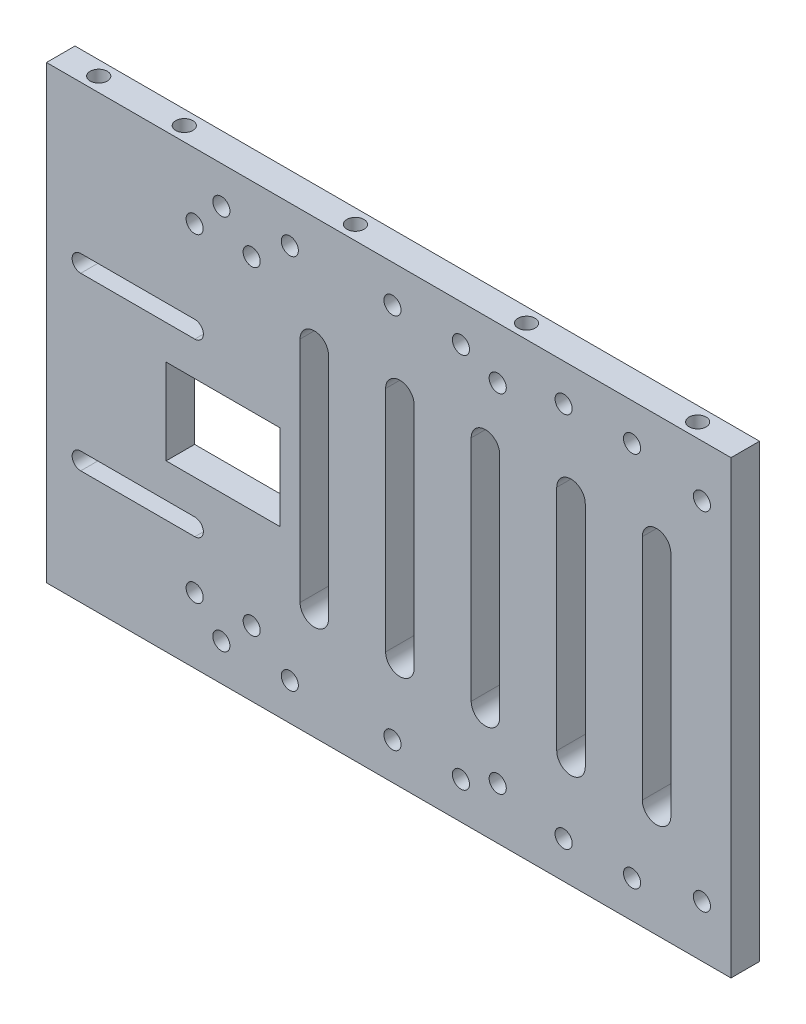
SolidWorks part; units mm, degrees
ref_plane "前视基准面" through (0, 0, 0) normal (0, 0, 1) x (1, 0, 0)
ref_plane "上视基准面" through (0, 0, 0) normal (0, 1, 0) x (1, 0, 0)
ref_plane "右视基准面" through (0, 0, 0) normal (1, 0, 0) x (0, 0, -1)
other "Configuration Table"
sketch "草图1" plane through (0, 0, 0) normal (0, 0, 1) x (1, 0, 0)
  line L1 (-60, -39.5) -> (60, -39.5)
  line L2 (-60, -39.5) -> (-60, 39.5)
  line L3 (-60, 39.5) -> (60, 39.5)
  line L4 (60, -39.5) -> (60, 39.5)
  line L5 (-60, -39.5) -> (60, 39.5) construction
  line L6 (-60, 39.5) -> (60, -39.5) construction
  point P0 (0, 0)
  dimension "D1" = 79
  dimension "D2" = 120
extrude "凸台-拉伸1" add sketch "草图1" along normal blind 5
sketch "草图2" plane through (0, 0, 0) normal (0, 0, -1) x (-1, 0, 0)
  circle A0 centre (-42.656, -33) radius 3.1
  circle A1 centre (-30.656, -33) radius 3.1
extrude "切除-拉伸1" cut sketch "草图2" against normal blind 2
sketch "草图3" plane through (0, 0, 2) normal (0, 0, -1) x (-1, 0, 0)
  circle A0 centre (-42.656, -33) radius 1.5
  circle A1 centre (-30.656, -33) radius 1.5
extrude "切除-拉伸2" cut sketch "草图3" against normal through all
pattern_linear "阵列(线性)1" count 3 spacing 30 along (-1, 0, 0) of "切除-拉伸1", "切除-拉伸2"
mirror "镜向2" about plane through (0, 0, 0) normal (0, 1, 0) of "阵列(线性)1"
sketch "草图4" plane through (0, 0, 0) normal (0, 0, -1) x (-1, 0, 0)
  line L0 (34, 12) -> (54, 12) construction
  line L1 (34, 15.1) -> (54, 15.1)
  line L2 (34, 8.9) -> (54, 8.9)
  line L3 (60, 39.5) -> (60, -39.5) construction
  line L4 (34.3421, -3) -> (54.815, -3) construction
  line L5 (34.3421, 17) -> (34.3421, -23) construction
  line L6 (54.815, 17) -> (54.815, -6) construction
  line L7 (34, -18) -> (54, -18) construction
  line L8 (34, -21.1) -> (54, -21.1)
  line L9 (34, -14.9) -> (54, -14.9)
  arc A4 (34, 15.1) -> (34, 8.9) centre (34, 12) ccw
  arc A5 (54, 8.9) -> (54, 15.1) centre (54, 12) ccw
  arc A6 (34, -21.1) -> (34, -14.9) centre (34, -18) cw
  arc A7 (54, -14.9) -> (54, -21.1) centre (54, -18) cw
  point P8 (44, 12)
  point P17 (44, -18)
  dimension "D1" = 20
  dimension "D2" = 6
extrude "切除-拉伸3" cut sketch "草图4" against normal blind 1.5
sketch "草图5" plane through (0, 0, 1.5) normal (0, 0, -1) x (-1, 0, 0)
  line L0 (54, 12) -> (34, 12) construction
  line L1 (54, 10.5) -> (34, 10.5)
  line L2 (54, 13.5) -> (34, 13.5)
  line L3 (60, 39.5) -> (60, -39.5) construction
  line L4 (34.3421, -3) -> (54.815, -3) construction
  line L5 (54.815, 17) -> (54.815, -6) construction
  line L6 (54, -18) -> (34, -18) construction
  line L7 (54, -16.5) -> (34, -16.5)
  line L8 (54, -19.5) -> (34, -19.5)
  arc A0 (54, 10.5) -> (54, 13.5) centre (54, 12) ccw
  arc A1 (34, 13.5) -> (34, 10.5) centre (34, 12) ccw
  arc A2 (54, -16.5) -> (54, -19.5) centre (54, -18) cw
  arc A3 (34, -19.5) -> (34, -16.5) centre (34, -18) cw
  point P4 (44, 12)
  point P18 (44, -18)
  dimension "D1" = 20
  dimension "D2" = 6
extrude "切除-拉伸4" cut sketch "草图5" against normal through all
sketch "草图7" plane through (0, -39.5, 0) normal (0, -1, 0) x (1, 0, 0)
  line L0 (46.656, 31) -> (46.656, 5) construction
  circle A0 centre (51.656, 2.5) radius 1.5
  circle A1 centre (21.656, 2.5) radius 1.5
  circle A2 centre (-8.344, 2.5) radius 1.5
  circle A3 centre (-38.344, 2.5) radius 1.5
  circle A4 centre (-53.344, 2.5) radius 1.5
  dimension "D1" = 5
  dimension "D2" = 15
extrude "切除-拉伸6" cut sketch "草图7" against normal blind 5
mirror "镜向3" about plane through (0, 0, 0) normal (0, 1, 0) of "切除-拉伸6"
sketch "草图9" plane through (0, 0, 0) normal (0, 0, -1) x (-1, 0, 0)
  line L0 (-46.9526, -20.2662) -> (-46.9526, 19.7338) construction
  line L1 (-49.4526, -20.2662) -> (-49.4526, 19.7338)
  line L2 (-44.4526, -20.2662) -> (-44.4526, 19.7338)
  line L3 (-31.9526, -20.2662) -> (-31.9526, 19.7338) construction
  line L4 (-34.4526, -20.2662) -> (-34.4526, 19.7338)
  line L5 (-29.4526, -20.2662) -> (-29.4526, 19.7338)
  line L6 (-16.9526, -20.2662) -> (-16.9526, 19.7338) construction
  line L7 (-19.4526, -20.2662) -> (-19.4526, 19.7338)
  line L8 (-14.4526, -20.2662) -> (-14.4526, 19.7338)
  line L9 (-1.9526, -20.2662) -> (-1.9526, 19.7338) construction
  line L10 (-4.4526, -20.2662) -> (-4.4526, 19.7338)
  line L11 (0.5474, -20.2662) -> (0.5474, 19.7338)
  line L12 (13.0474, -20.2662) -> (13.0474, 19.7338) construction
  line L13 (10.5474, -20.2662) -> (10.5474, 19.7338)
  line L14 (15.5474, -20.2662) -> (15.5474, 19.7338)
  circle A0 centre (24.0277, -28) radius 1.5 construction
  circle A1 centre (34.0277, -28) radius 1.5 construction
  circle A2 centre (24.0277, 28) radius 1.5 construction
  circle A3 centre (34.0277, 28) radius 1.5 construction
  circle A4 centre (24.0277, -28) radius 1.5
  circle A5 centre (34.0277, -28) radius 1.5
  circle A6 centre (24.0277, 28) radius 1.5
  circle A7 centre (34.0277, 28) radius 1.5
  arc A8 (-49.4526, -20.2662) -> (-44.4526, -20.2662) centre (-46.9526, -20.2662) ccw
  arc A9 (-44.4526, 19.7338) -> (-49.4526, 19.7338) centre (-46.9526, 19.7338) ccw
  arc A10 (-34.4526, -20.2662) -> (-29.4526, -20.2662) centre (-31.9526, -20.2662) ccw
  arc A11 (-29.4526, 19.7338) -> (-34.4526, 19.7338) centre (-31.9526, 19.7338) ccw
  circle A16 centre (-19.1038, 30.4) radius 1.5
  circle A17 centre (-54.9038, 30.4) radius 1.5
  circle A18 centre (-19.1038, -30.4) radius 1.5
  circle A19 centre (-54.9038, -30.4) radius 1.5
  arc A20 (-19.4526, -20.2662) -> (-14.4526, -20.2662) centre (-16.9526, -20.2662) ccw
  arc A21 (-14.4526, 19.7338) -> (-19.4526, 19.7338) centre (-16.9526, 19.7338) ccw
  arc A22 (-4.4526, -20.2662) -> (0.5474, -20.2662) centre (-1.9526, -20.2662) ccw
  arc A23 (0.5474, 19.7338) -> (-4.4526, 19.7338) centre (-1.9526, 19.7338) ccw
  arc A24 (10.5474, -20.2662) -> (15.5474, -20.2662) centre (13.0474, -20.2662) ccw
  arc A25 (15.5474, 19.7338) -> (10.5474, 19.7338) centre (13.0474, 19.7338) ccw
  point P17 (-46.9526, -0.2662)
  point P31 (-31.9526, -0.2662)
  point P38 (-16.9526, -0.2662)
  point P45 (-1.9526, -0.2662)
  point P52 (13.0474, -0.2662)
  dimension "D1" = 5
extrude "切除-拉伸7" cut sketch "草图9" against normal through all
sketch "草图11" plane through (0, 0, 5) normal (0, 0, 1) x (1, 0, 0)
  line L0 (-29.0277, 4.5) -> (-29.0277, -10.5)
  line L4 (-39.0277, -10.5) -> (-19.0277, -10.5)
  line L5 (-19.0277, -10.5) -> (-19.0277, 4.5)
  line L6 (-19.0277, 4.5) -> (-39.0277, 4.5)
  line L7 (-39.0277, 4.5) -> (-39.0277, -10.5)
  line L8 (-39.0277, -10.5) -> (-19.0277, -10.5)
  line L9 (-19.0277, -10.5) -> (-19.0277, 4.5)
  line L10 (-19.0277, 4.5) -> (-39.0277, 4.5)
  line L11 (-39.0277, 4.5) -> (-39.0277, -10.5)
  dimension "D1" = 0
extrude "切除-拉伸8" cut sketch "草图11" against normal through all contours L9 L10 L0 L8 | L10 L11 L8 L0 region at (-24.0277, -3, 5) region at (-34.0277, -3, 5)
